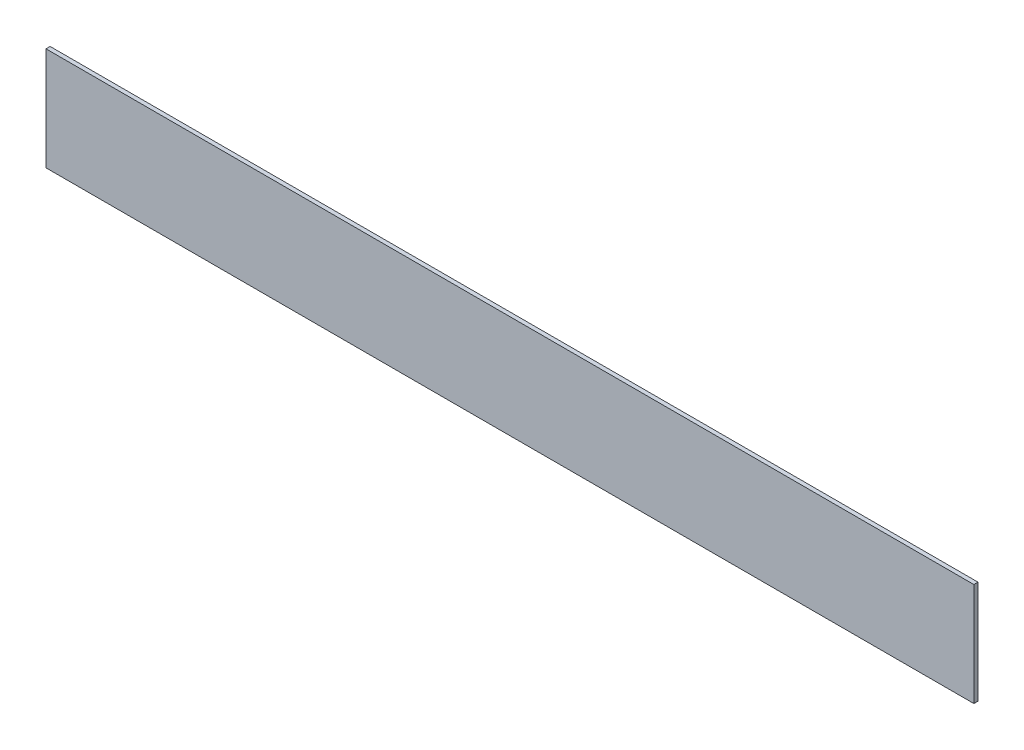
SolidWorks part; units mm, degrees
material "1345 Alloy"
ref_plane "Front Plane" through (0, 0, 0) normal (0, 0, 1) x (1, 0, 0)
ref_plane "Top Plane" through (0, 0, 0) normal (0, 1, 0) x (1, 0, 0)
ref_plane "Right Plane" through (0, 0, 0) normal (1, 0, 0) x (0, 0, -1)
sketch "Sketch1" plane through (0, 0, 0) normal (0, 0, 1) x (1, 0, 0)
  line L1 (-225, 25) -> (225, 25)
  line L2 (-225, 25) -> (-225, -25)
  line L3 (-225, -25) -> (225, -25)
  line L4 (225, 25) -> (225, -25)
  line L5 (-225, 25) -> (225, -25) construction
  line L6 (-225, -25) -> (225, 25) construction
  point P0 (0, 0)
  dimension "D1" = 450
  dimension "D2" = 50
extrude "Boss-Extrude1" add sketch "Sketch1" along normal blind 2
